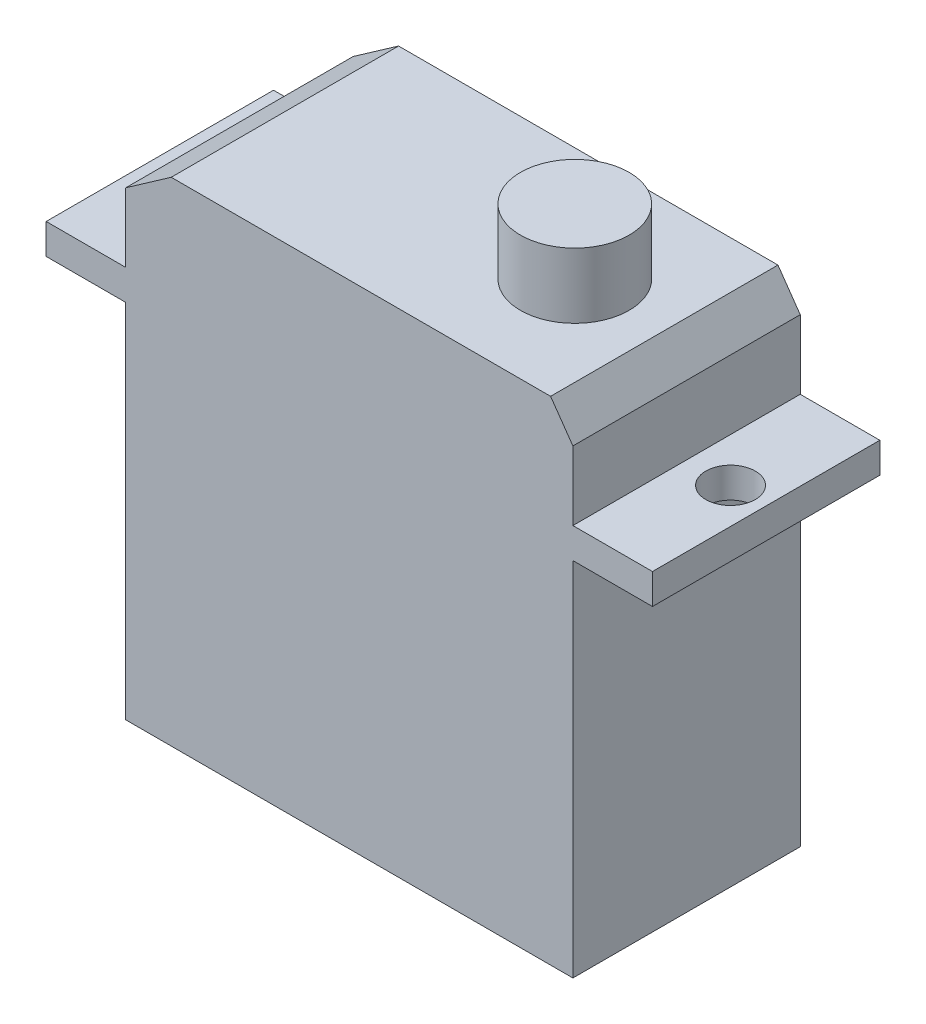
SolidWorks part; units mm, degrees
material "6061-T6 (SS)"
ref_plane "XY" through (0, 0, 0) normal (0, 0, 1) x (1, 0, 0)
ref_plane "XZ" through (0, 0, 0) normal (0, 1, 0) x (1, 0, 0)
ref_plane "YZ" through (0, 0, 0) normal (1, 0, 0) x (0, 0, -1)
ref_axis "X" through (-88.99, 0, 0) along (1, 0, 0)
ref_axis "Y" through (0, -55, 0) along (0, 1, 0)
ref_axis "Z" through (0, 0, 55) along (0, 0, -1)
sketch "Sketch1" plane through (0, 0, 0) normal (0, 0, 1) x (1, 0, 0)
  line L0 (-14.75, 11.925) -> (-20, 11.925)
  line L1 (-14.75, -11.925) -> (14.75, -11.925)
  line L2 (-14.75, -11.925) -> (-14.75, 11.925)
  line L4 (14.75, -11.925) -> (14.75, 11.925)
  line L5 (-14.75, -11.925) -> (14.75, 11.925) construction
  line L6 (-14.75, 11.925) -> (14.75, -11.925) construction
  line L7 (-20, 11.925) -> (-20, 13.925)
  line L8 (-20, 13.925) -> (-14.75, 13.925)
  line L9 (-14.75, 13.925) -> (-14.75, 18.4744)
  line L10 (-14.75, 18.4744) -> (-11.75, 20.575)
  line L11 (-11.75, 20.575) -> (13.2791, 20.575)
  line L12 (13.2791, 20.575) -> (14.75, 18.4744)
  line L13 (14.75, 18.4744) -> (14.75, 13.925)
  line L14 (14.75, 13.925) -> (20, 13.925)
  line L15 (20, 13.925) -> (20, 11.925)
  line L16 (20, 11.925) -> (14.75, 11.925)
  point P0 (0, 0)
  dimension "D1" = 23.85
  dimension "D2" = 29.5
  dimension "D3" = 8.65
  dimension "D4" = 40
  dimension "D5" = 2
  dimension "D6" = 125
  dimension "D7" = 3
extrude "Boss-Extrude1" add sketch "Sketch1" along normal mid plane 15
sketch "Sketch2" plane through (0, 20.575, 0) normal (0, 1, 0) x (1, 0, 0)
  line L0 (0, 0) -> (14.75, 0) construction
  line L1 (14.75, -7.5) -> (14.75, 7.5) construction
  circle A0 centre (7.375, 0) radius 3.5871
extrude "Boss-Extrude2" add sketch "Sketch2" along normal blind 4.3
hole_wizard "#4 Clearance Hole1" positions "Sketch3" profile "Sketch4" hole size "#4" standard "ANSI Inch"
sketch "Sketch3" plane through (0, 13.925, 0) normal (0, 1, 0) x (1, 0, 0)
  line L0 (-17.65, 0) -> (17.65, 0) construction
  point P0 (-17.65, 0)
  point P2 (17.65, 0)
  dimension "D1" = 35.3
sketch "Sketch4" plane through (-17.65, 13.925, 0) normal (1, 0, 0) x (0, 0, 1)
  line L0 (0, 0) -> (0, 6.8206)
  line L1 (0, 6.8206) -> (1.6319, 5.84)
  line L2 (1.6319, 5.84) -> (1.6319, 0)
  line L5 (1.6319, 0) -> (0, 0)
  line L10 (0, 6.8206) -> (-1.632, 5.84) construction
  line L11 (0, -6.35) -> (0, 107.95) construction
  dimension "Hole Dia." = 3.2639
  dimension "Hole Depth" = 5.84
  dimension "Drill Angle" = 118
